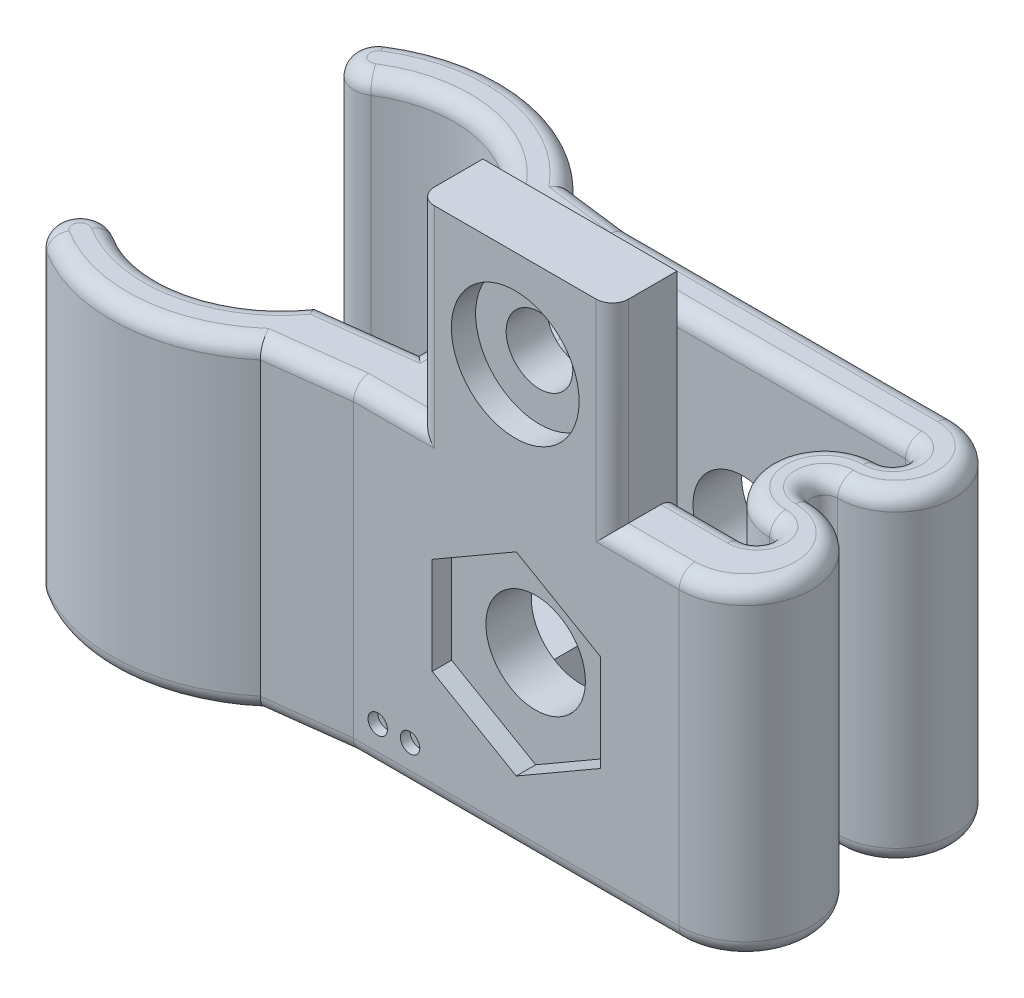
SolidWorks part; units mm, degrees
ref_plane "Front Plane" through (0, 0, 0) normal (0, 0, 1) x (1, 0, 0)
ref_plane "Top Plane" through (0, 0, 0) normal (0, 1, 0) x (1, 0, 0)
ref_plane "Right Plane" through (0, 0, 0) normal (1, 0, 0) x (0, 0, -1)
sketch "Sketch2" plane through (0, 0, 0) normal (0, 1, 0) x (1, 0, 0)
  line L0 (0, 0) -> (32, 0) construction
  line L1 (0, 0) -> (0, 1.6) construction
  line L2 (0, 0) -> (0, -1.6) construction
  line L3 (32, 0) -> (32, 5) construction
  line L4 (32, 0) -> (32, -5) construction
  line L5 (32, 5) -> (6, 5) construction
  line L6 (32, -5) -> (6, -5) construction
  line L7 (11.8739, 5) -> (32, 5)
  line L8 (11.8739, -5) -> (32, -5)
  line L9 (32, 8) -> (11.8739, 8)
  line L10 (32, -9) -> (11.8739, -9)
  line L11 (11.8739, 5) -> (6.2801, 5.7)
  line L12 (11.8739, 8) -> (7.919, 8.4949)
  line L13 (11.8739, -5) -> (6.2801, -5.7)
  line L14 (11.8739, -9) -> (6.7523, -9.6409)
  arc A0 (6.2801, 5.7) -> (-4, 7.9443) centre (0, 1.6) ccw
  arc A1 (6.2801, -5.7) -> (-4, -7.9443) centre (0, -1.6) cw
  arc A2 (32, 5) -> (32, 3.4) centre (32, 4.2) cw
  arc A3 (32, 3.4) -> (32, -3.4) centre (32, 0) ccw
  arc A4 (32, -3.4) -> (32, -5) centre (32, -4.2) cw
  arc A5 (-4, 7.9443) -> (-5.6, 10.482) centre (-4.8, 9.2131) cw
  arc A6 (-4, -7.9443) -> (-5.6, -10.482) centre (-4.8, -9.2131) ccw
  arc A7 (-5.6, 10.482) -> (7.919, 8.4949) centre (0, 1.6) cw
  arc A8 (-5.6, -10.482) -> (6.7523, -9.6409) centre (0, -1.6) ccw
  arc A9 (32, -9) -> (32, -0.8) centre (32, -4.9) ccw
  arc A10 (32, -0.8) -> (32, 0.8) centre (32, 0) cw
  arc A11 (32, 0.8) -> (32, 8) centre (32, 4.4) ccw
  dimension "D6" = 7.5
  dimension "D7" = 7.5
  dimension "D8" = 0.8
  dimension "D9" = 0.8
  dimension "D11" = 1.5
  dimension "D12" = 1.5
  dimension "D14" = 10.5
  dimension "D16" = 10.5
  dimension "D17" = 0.8
  dimension "D18" = 11.8739
  dimension "D1" = 1.6
  dimension "D2" = 1.6
  dimension "D3" = 32
  dimension "D4" = 5
  dimension "D5" = 5
  dimension "D10" = 4
  dimension "D13" = 3
  dimension "D15" = 4
  dimension "D19" = 0.7
extrude "Boss-Extrude1" add sketch "Sketch2" along normal blind 20
sketch "Sketch3" plane through (0, 0, -8) normal (0, 0, -1) x (-1, 0, 0)
  line L0 (-21.9369, 20) -> (-21.9369, 0) construction
  line L1 (-32, 20) -> (-11.8739, 20) construction
  line L2 (-32, 0) -> (-11.8739, 0) construction
  circle A0 centre (-21.9369, 10) radius 3.075
  dimension "D1" = 6.15
extrude "Cut-Extrude1" cut sketch "Sketch3" against normal through all
sketch "Sketch4" plane through (0, 0, 9) normal (0, 0, 1) x (1, 0, 0)
  line L0 (21.9369, 6.925) -> (21.9369, 13.075) construction
  line L2 (21.9369, 4) -> (27.1331, 7)
  line L3 (27.1331, 7) -> (27.1331, 13)
  line L4 (27.1331, 13) -> (21.9369, 16)
  line L5 (21.9369, 16) -> (16.7408, 13)
  line L6 (16.7408, 13) -> (16.7408, 7)
  line L7 (16.7408, 7) -> (21.9369, 4)
  circle A0 centre (21.9369, 10) radius 3.075 construction
  circle A1 centre (21.9369, 10) radius 6 construction
  dimension "D1" = 12
extrude "Cut-Extrude2" cut sketch "Sketch4" against normal blind 1.2
sketch "Sketch5" plane through (0, 20, 0) normal (0, 1, 0) x (1, 0, 0)
  line L0 (32, -5) -> (11.8739, -5) construction
  line L1 (27.8739, -9) -> (15.8739, -9)
  line L2 (27.8739, -9) -> (27.8739, -5)
  line L3 (27.8739, -5) -> (15.8739, -5)
  line L4 (15.8739, -9) -> (15.8739, -5)
  dimension "D1" = 12
  dimension "D2" = 4
extrude "Boss-Extrude2" add sketch "Sketch5" along normal blind 12
sketch "Sketch6" plane through (0, 0, 9) normal (0, 0, 1) x (1, 0, 0)
  line L0 (15.8739, 26) -> (27.8739, 26) construction
  line L1 (15.8739, 32) -> (15.8739, 20) construction
  line L2 (27.8739, 32) -> (27.8739, 20) construction
  circle A0 centre (21.8739, 26) radius 2.06
  dimension "D1" = 4.12
extrude "Cut-Extrude3" cut sketch "Sketch6" against normal through all
sketch "Sketch7" plane through (0, 0, 0) normal (0, -1, 0) x (1, 0, 0)
  line L0 (11.8739, 5) -> (11.8739, -1.6)
  line L1 (32, 5) -> (11.8739, 5) construction
  line L2 (16.8739, 5) -> (16.8739, -2.1)
  line L3 (11.8739, 5) -> (16.8739, 5)
  line L4 (11.8739, -1.6) -> (16.8739, -2.1)
  dimension "D1" = 11.8739
  dimension "D2" = 6.6
  dimension "D3" = 7.1
  dimension "D4" = 5
extrude "Boss-Extrude3" add sketch "Sketch7" against normal blind 4
extrude "Boss-Extrude4" add sketch "Sketch7<2>" against normal blind 4 from offset 16 offset against normal yes
sketch "Sketch7<2>" plane through (0, 0, 0) normal (0, -1, 0) x (1, 0, 0) same geometry as "Sketch7"
sketch "Sketch8" plane through (0, 0, 9) normal (0, 0, 1) x (1, 0, 0)
  circle A0 centre (21.8739, 26) radius 3.95
  dimension "D1" = 7.9
extrude "Cut-Extrude4" cut sketch "Sketch8" against normal blind 1.5
fillet "Fillet1" radius 1 23 edges at (28.6, 0, 0) (32.8, 0, 4.2) (24.4369, 0, 5) (16.8739, 0, 1.45) (14.3739, 0, -1.85) (11.8739, 0, 1.7) (1.5997, 0, 8.9274) (-6.0689, 0, 8.4131) (0.7133, 0, 12.0757) (21.9369, 0, 9) (36.1, 0, 4.9) (31.2, 0, 0) (35.6, 0, -4.4) (21.9369, 0, -8) (1.5269, 0, -11.9884) (-6.0689, 0, -8.4131) (1.5997, 0, -8.9274) (21.9369, 0, -5) (32.8, 0, -4.2) (9.8964, 0, -8.2475) (9.077, 0, -5.35) (9.077, 0, 5.35) (9.3131, 0, 9.3205)
fillet "Fillet7" radius 1 2 edges
fillet "Fillet10" radius 1 15 edges at (21.9369, 20, -8) (35.6, 20, -4.4) (31.2, 20, 0) (36.1, 20, 4.9) (32.8, 20, 4.2) (28.6, 20, 0) (32.8, 20, -4.2) (21.9369, 20, -5) (9.077, 20, -5.35) (1.5997, 20, -8.9274) (-6.0689, 20, -8.4131) (1.5269, 20, -11.9884) (9.8964, 20, -8.2475)
fillet "Fillet11" radius 1 9 edges at (9.3131, 20, 9.3205) (0.7133, 20, 12.0757) (-6.0689, 20, 8.4131) (1.5997, 20, 8.9274) (9.077, 20, 5.35) (16.8739, 20, 1.45) (14.3739, 20, -1.85) (11.8739, 20, 1.7)
sketch "Sketch9" plane through (0, 0, 9) normal (0, 0, 1) x (1, 0, 0)
  line L0 (11.8739, 1) -> (32, 1) construction
  line L1 (11.8739, 19) -> (11.8739, 1) construction
  circle A0 centre (13.3739, 2.5) radius 0.6
  circle A1 centre (15.3739, 2.5) radius 0.6
  dimension "D1" = 1.2
  dimension "D4" = 1.2
  dimension "D2" = 1.5
  dimension "D3" = 1.5
  dimension "D5" = 2
extrude "Cut-Extrude5" cut sketch "Sketch9" against normal blind 0.6
